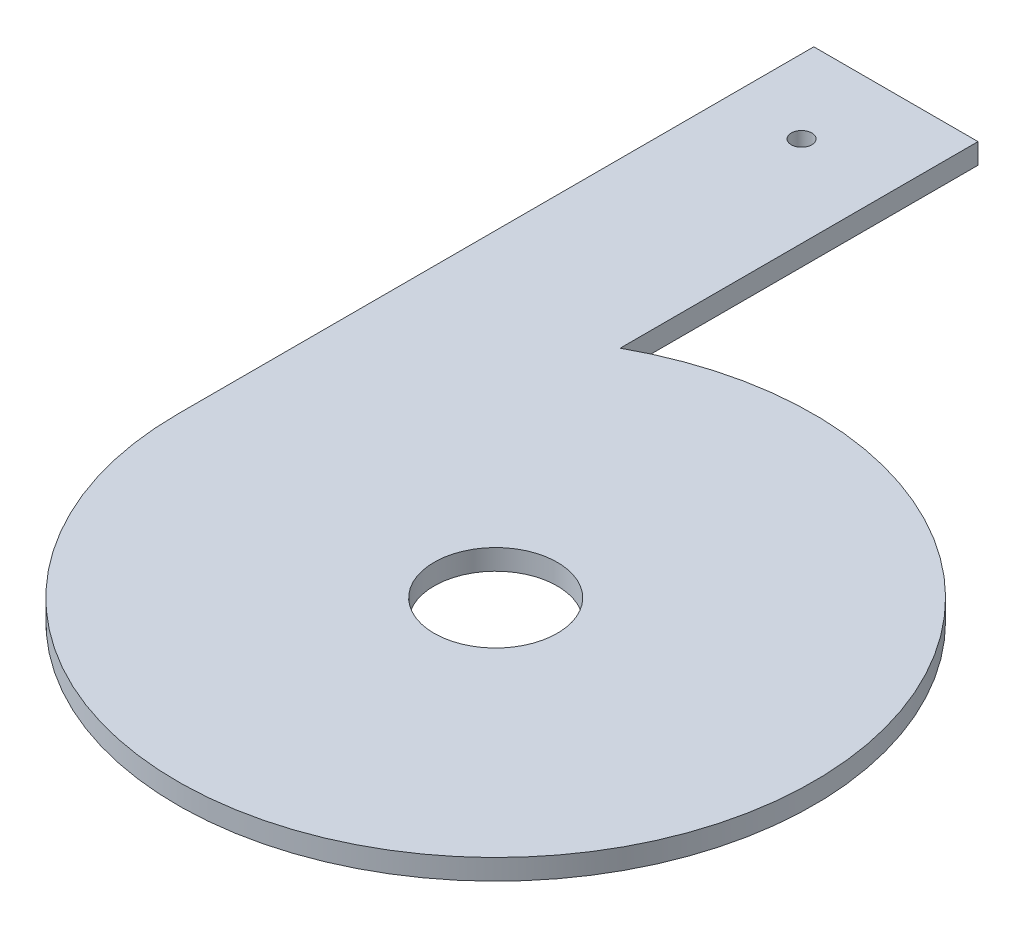
SolidWorks part; units mm, degrees
ref_plane "Front Plane" through (0, 0, 0) normal (0, 0, 1) x (1, 0, 0)
ref_plane "Top Plane" through (0, 0, 0) normal (0, 1, 0) x (1, 0, 0)
ref_plane "Right Plane" through (0, 0, 0) normal (1, 0, 0) x (0, 0, -1)
sketch "Sketch1" plane through (0, 0, 0) normal (0, 1, 0) x (1, 0, 0)
  circle A0 centre (0, 0) radius 31
extrude "Boss-Extrude1" add sketch "Sketch1" along normal blind 2
sketch "Sketch2" plane through (0, 2, 0) normal (0, 1, 0) x (1, 0, 0)
  circle A0 centre (0, 0) radius 6
extrude "Cut-Extrude1" cut sketch "Sketch2" against normal blind 2
sketch "Sketch3" plane through (0, 2, 0) normal (0, 1, 0) x (1, 0, 0)
  line L1 (-31, 0) -> (-15, 0)
  line L2 (-31, 0) -> (-31, 62)
  line L3 (-31, 62) -> (-15, 62)
  line L4 (-15, 0) -> (-15, 62)
  circle A0 centre (0, 0) radius 31 construction
  dimension "D1" = 62
  dimension "D2" = 16
extrude "Boss-Extrude2" add sketch "Sketch3" against normal blind 2
sketch "Sketch4" plane through (0, 2, 0) normal (0, 1, 0) x (1, 0, 0)
  line L3 (-15, 27.1293) -> (-15, 62)
  line L4 (-15, 62) -> (-31, 62)
  line L5 (-31, 62) -> (-31, 0)
  line L6 (-15, 27.1293) -> (-15, 62)
  line L7 (-15, 62) -> (-31, 62)
  line L8 (-31, 62) -> (-31, 0)
  line L10 (-20.007, 48.3271) -> (-20.0089, 61.2271)
  line L11 (-25.907, 48.3262) -> (-20.007, 48.3271)
  line L12 (-25.9089, 61.2262) -> (-25.907, 48.3262)
  line L13 (-20.0089, 61.2271) -> (-25.9089, 61.2262)
  line L14 (-20.007, 48.3271) -> (-20.0089, 61.2271)
  line L15 (-25.907, 48.3262) -> (-20.007, 48.3271)
  line L16 (-25.9089, 61.2262) -> (-25.907, 48.3262)
  line L17 (-20.0089, 61.2271) -> (-25.9089, 61.2262)
  arc A1 (-31, 0) -> (-15, 27.1293) centre (0, 0) ccw
  arc A2 (-31, 0) -> (-15, 27.1293) centre (0, 0) ccw
  dimension "D1" = 0
  dimension "D2" = 0
sketch "Sketch6" plane through (0, 2, 0) normal (0, 1, 0) x (1, 0, 0)
  line L4 (-20.007, 48.3271) -> (-20.0089, 61.2271)
  line L5 (-25.907, 48.3262) -> (-20.007, 48.3271)
  line L6 (-25.9089, 61.2262) -> (-25.907, 48.3262)
  line L7 (-20.0089, 61.2271) -> (-25.9089, 61.2262)
  line L8 (-20.007, 48.3271) -> (-20.0089, 61.2271)
  line L9 (-25.907, 48.3262) -> (-20.007, 48.3271)
  line L10 (-25.9089, 61.2262) -> (-25.907, 48.3262)
  line L11 (-20.0089, 61.2271) -> (-25.9089, 61.2262)
  dimension "D1" = 0
sketch "Sketch8" plane through (0, 0, 0) normal (0, -1, 0) x (1, 0, 0)
  circle A0 centre (-23.8268, -53.6314) radius 1 construction
  circle A1 centre (-23.8268, -53.6314) radius 1
extrude "Cut-Extrude2" cut sketch "Sketch8" against normal up to next
